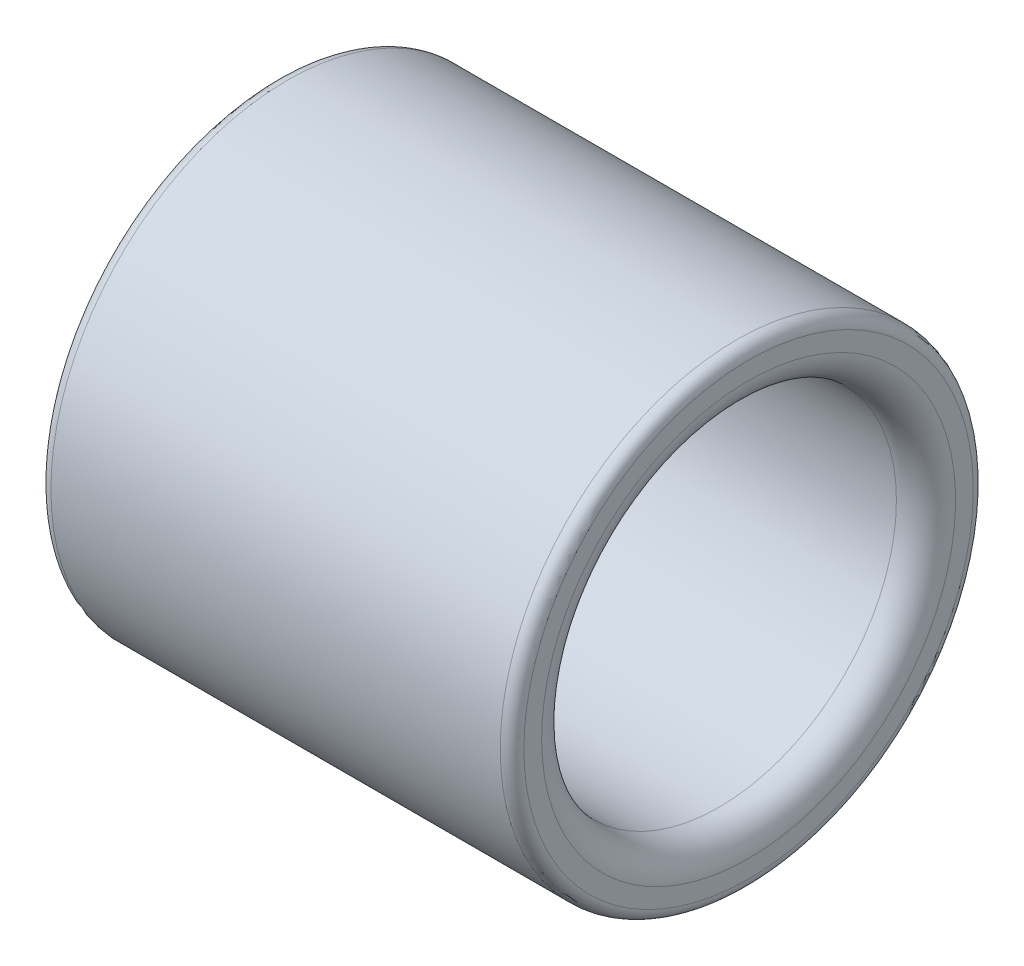
SolidWorks part; units mm, degrees
ref_plane "Front Plane" through (0, 0, 0) normal (0, 0, 1) x (1, 0, 0)
ref_plane "Top Plane" through (0, 0, 0) normal (0, 1, 0) x (1, 0, 0)
ref_plane "Right Plane" through (0, 0, 0) normal (1, 0, 0) x (0, 0, -1)
sketch "Sketch1" plane through (0, 0, 0) normal (0, 0, 1) x (1, 0, 0)
  line L0 (0, 0) -> (8, 0) construction
  line L1 (0, 3) -> (0, 4)
  line L2 (0, 4) -> (8, 4)
  line L4 (8, 4) -> (8, 3)
  line L6 (8, 3) -> (0, 3)
  dimension "L" = 8
  dimension "D_s" = 6
  dimension "D" = 8
revolve "Revolve1" add sketch "Sketch1" angle 360 about L0
chamfer "Chamfer1" [suppressed] distance 0.3 angle 45
chamfer "Chamfer2" [suppressed] distance 1 angle 15
chamfer "Chamfer3" [suppressed] distance 2 angle 10
fillet "Fillet1" [suppressed] radius 1
fillet "Fillet2" radius 0.2 2 edges at (8, 0, 4) (0, 0, 4)
fillet "Fillet3" radius 0.5 2 edges at (8, 0, 3) (0, 0, 3)
